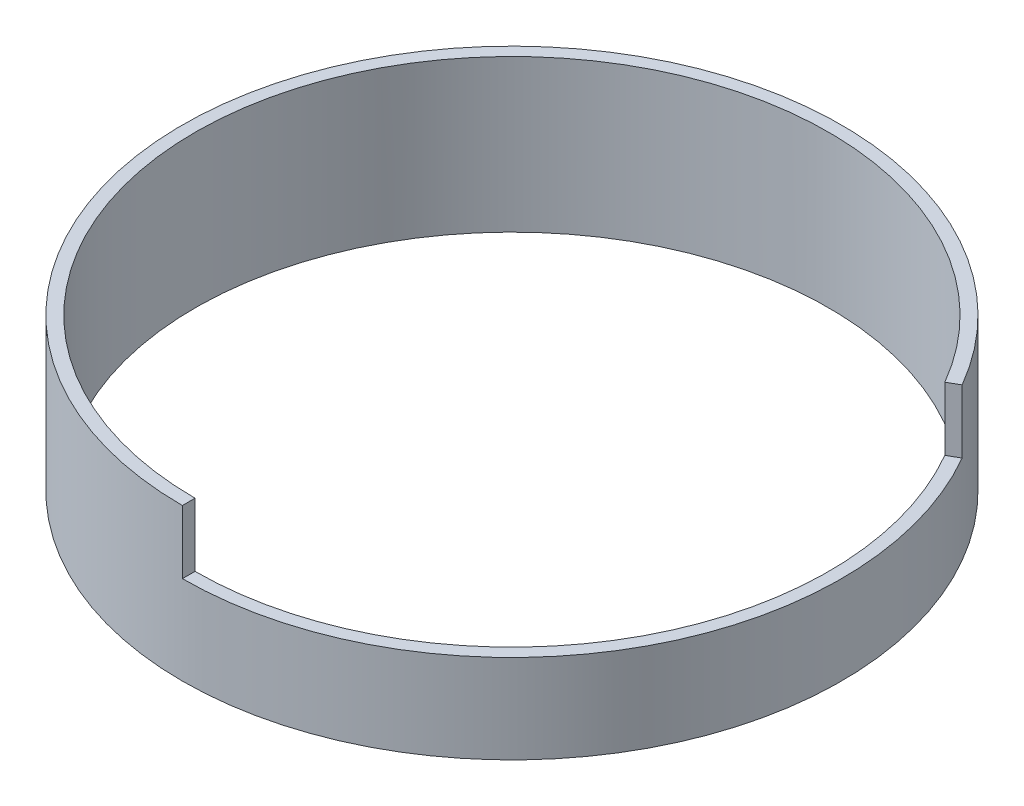
SolidWorks part; units mm, degrees
material "AISI 316 Stainless Steel Sheet (SS)"
ref_plane "Front Plane" through (0, 0, 0) normal (0, 0, 1) x (1, 0, 0)
ref_plane "Top Plane" through (0, 0, 0) normal (0, 1, 0) x (1, 0, 0)
ref_plane "Right Plane" through (0, 0, 0) normal (1, 0, 0) x (0, 0, -1)
sketch "Sketch1" plane through (0, 0, 0) normal (0, 1, 0) x (1, 0, 0)
  line L0 (0, -79.375) -> (0, -82.55)
  line L1 (68.7408, 39.6875) -> (71.4904, 41.275)
  circle A0 centre (0, 0) radius 79.375
  circle A1 centre (0, 0) radius 82.55
  dimension "D1" = 158.75
  dimension "D2" = 3.175
  dimension "D3" = 120
extrude "Boss-Extrude1" add sketch "Sketch1" along normal blind 38.1 contours L1 A1 L0 A0 region at (-2.258, 0, 80.9625)
extrude "Boss-Extrude2" add sketch "Sketch1<3>" along normal blind 22.225 contours L0 A1 L1 A0 region at (57.1789, 0, 57.1789)
sketch "Sketch1<3>" plane through (0, 0, 0) normal (0, 1, 0) x (1, 0, 0) same geometry as "Sketch1"
